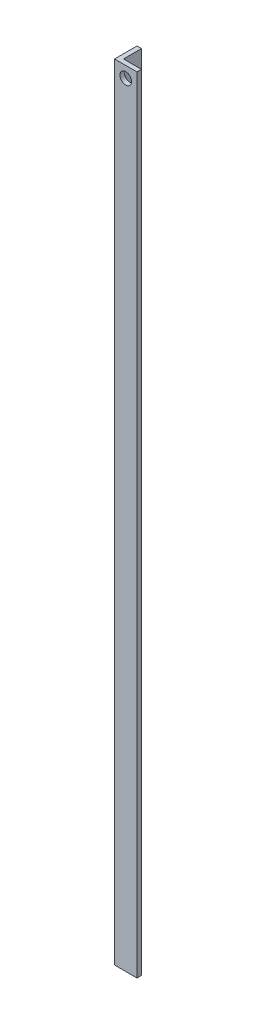
SolidWorks part; units mm, degrees
material "6061-T6 (SS)"
ref_plane "Front Plane" through (0, 0, 0) normal (0, 0, 1) x (1, 0, 0)
ref_plane "Top Plane" through (0, 0, 0) normal (0, 1, 0) x (1, 0, 0)
ref_plane "Right Plane" through (0, 0, 0) normal (1, 0, 0) x (0, 0, -1)
sketch "Sketch1" plane through (0, 0, 0) normal (0, 1, 0) x (1, 0, 0)
  line L0 (0, 0) -> (0, 10)
  line L1 (0, 10) -> (2, 10)
  line L2 (2, 10) -> (2, 2)
  line L3 (2, 2) -> (10, 2)
  line L4 (10, 2) -> (10, 0)
  line L5 (10, 0) -> (0, 0)
  dimension "D1" = 10
  dimension "D2" = 2
extrude "Boss-Extrude1" add sketch "Sketch1" along normal blind 350
hole_wizard "#6 (0.204) Diameter Hole2" positions "Sketch6" profile "Sketch7" hole size "#6" standard "ANSI Inch" end condition through all
sketch "Sketch6" plane through (0, 0, 0) normal (-1, 0, 0) x (0, 0, 1)
  line L0 (0, 350) -> (0, 0) construction
  line L1 (-10, 0) -> (0, 0) construction
  point P0 (-5, 5)
  dimension "D1" = 5
  dimension "D2" = 5
sketch "Sketch7" plane through (0, 5, -5) normal (0, 1, 0) x (0, 0, 1)
  line L0 (0, 0) -> (0, 10)
  line L1 (0, 10) -> (2.5908, 10)
  line L2 (2.5908, 10) -> (2.5908, 0)
  line L5 (2.5908, 0) -> (0, 0)
  line L11 (0, -6.35) -> (0, 107.95) construction
  dimension "Thru Hole Dia." = 5.1816
  dimension "Thru Hole Depth" = 10
hole_wizard "#6 (0.204) Diameter Hole3" positions "Sketch8" profile "Sketch9" hole size "#6" standard "ANSI Inch" end condition through all
sketch "Sketch8" plane through (0, 0, 0) normal (0, 0, 1) x (1, 0, 0)
  line L0 (0, 350) -> (0, 0) construction
  line L1 (0, 350) -> (10, 350) construction
  point P0 (5, 345)
  dimension "D1" = 5
  dimension "D2" = 5
sketch "Sketch9" plane through (5, 345, 0) normal (1, 0, 0) x (0, -1, 0)
  line L0 (0, 0) -> (0, 10)
  line L1 (0, 10) -> (2.5908, 10)
  line L2 (2.5908, 10) -> (2.5908, 0)
  line L5 (2.5908, 0) -> (0, 0)
  line L11 (0, -6.35) -> (0, 107.95) construction
  dimension "Thru Hole Dia." = 5.1816
  dimension "Thru Hole Depth" = 10
